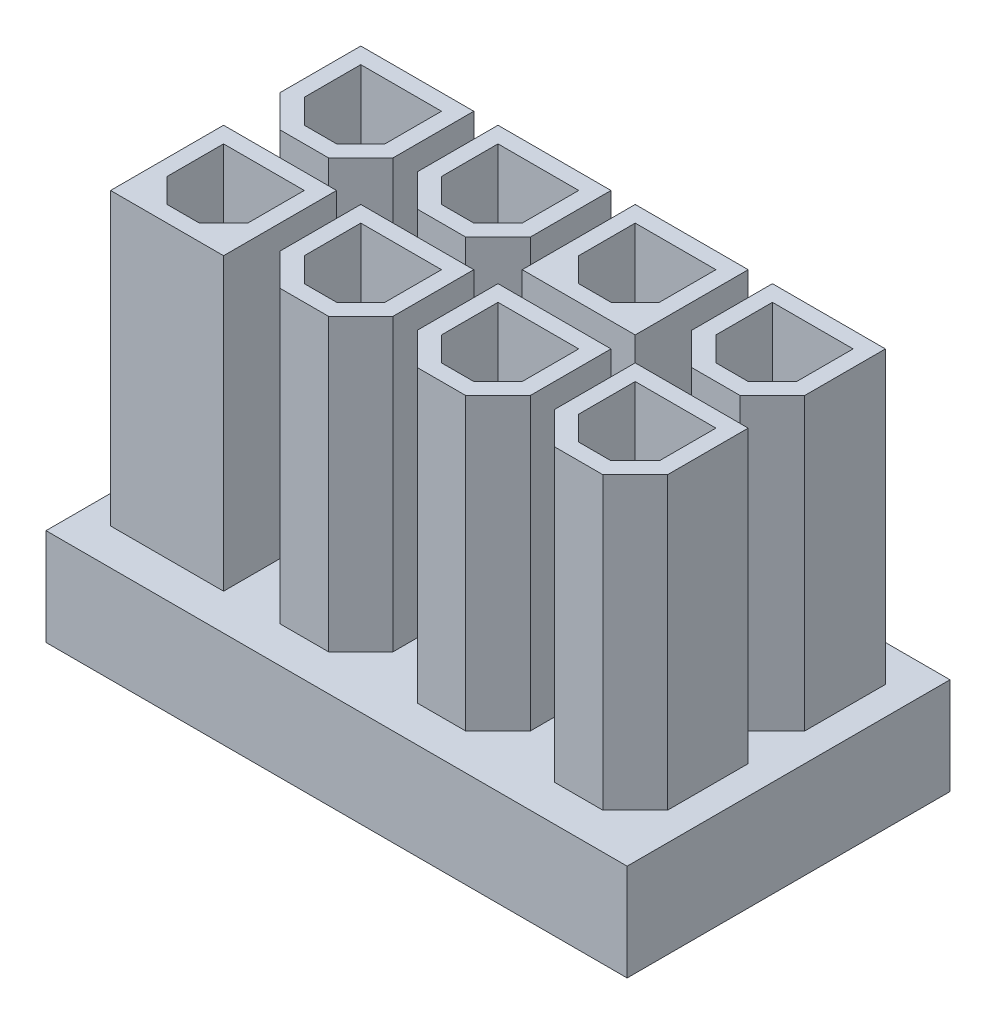
SolidWorks part; units mm, degrees
ref_plane "Ebene vorne" through (0, 0, 0) normal (0, 0, 1) x (1, 0, 0)
ref_plane "Ebene oben" through (0, 0, 0) normal (0, 1, 0) x (1, 0, 0)
ref_plane "Ebene rechts" through (0, 0, 0) normal (1, 0, 0) x (0, 0, -1)
sketch "Skizze1" plane through (0, 0, 0) normal (1, 0, 0) x (0, 0, -1)
  line L1 (5, 0) -> (-5, 0)
  line L2 (5, 0) -> (5, 11)
  line L3 (5, 11) -> (-5, 11)
  line L4 (-5, 0) -> (-5, 11)
  point P4 (0, 0)
  dimension "D1" = 10
  dimension "D2" = 11
extrude "Aufsatz-Linear austragen1" add sketch "Skizze1" along normal mid plane 18
sketch "Skizze2" plane through (0, 0, 0) normal (1, 0, 0) x (0, 0, -1)
  line L0 (0, 0) -> (0, 11) construction
  line L1 (-5, 0) -> (-6.5, 0)
  line L2 (-5, 0) -> (-5, 1)
  line L3 (-5, 1) -> (-6.5, 1)
  line L4 (-6.5, 0) -> (-6.5, 1)
  line L5 (5, 11) -> (-5, 11) construction
  line L6 (6.5, 0) -> (6.5, 1)
  line L7 (5, 1) -> (6.5, 1)
  line L8 (5, 0) -> (5, 1)
  line L9 (5, 0) -> (6.5, 0)
  dimension "D1" = 1.5
  dimension "D2" = 1
extrude "Aufsatz-Linear austragen2" add sketch "Skizze2" along normal mid plane 18
sketch "Skizze3" plane through (0, 0, 0) normal (1, 0, 0) x (0, 0, -1)
  line L0 (5, 11) -> (5.5717, 11)
  line L1 (7.5, 8.198) -> (7.5, 5.198)
  line L2 (7.5, 5.198) -> (8.5, 4)
  line L3 (8.5, 4) -> (8.5, 2)
  line L4 (8.5, 2) -> (6.5, 2)
  line L5 (6.5, 2) -> (6.5, 8)
  line L6 (6.5, 8) -> (5, 8)
  line L7 (5, 1) -> (5, 11) construction
  line L8 (5, 11) -> (5, 8)
  line L9 (-6.5, 0) -> (6.5, 0) construction
  arc A0 (5.5717, 11) -> (6.5359, 9.599) centre (7.0717, 11) ccw
  arc A1 (6.5359, 9.599) -> (7.5, 8.198) centre (6, 8.198) cw
  dimension "D5" = 1.5
  dimension "D1" = 2
  dimension "D2" = 1
  dimension "D3" = 2
  dimension "D4" = 2
  dimension "D6" = 3
  dimension "D7" = 1.5
  dimension "D8" = 3
extrude "Aufsatz-Linear austragen3" [suppressed] add sketch "Skizze3" along normal mid plane 8
sketch "Skizze4" [suppressed] plane through (0, 0, 0) normal (0, -1, 0) x (1, 0, 0)
  line L0 (9, -5) -> (-9, -5) construction
  line L1 (-2.5, -5) -> (2.5, -5)
  line L2 (-2.5, -5) -> (-2.5, -6.5)
  line L3 (-2.5, -6.5) -> (2.5, -6.5)
  line L4 (2.5, -5) -> (2.5, -6.5)
  line L5 (9, -6.5) -> (-9, -6.5) construction
  line L6 (0, -5) -> (0, 0) construction
  line L7 (-4, -6.5) -> (-4, -8.5) construction
  dimension "D1" = 1.5
extrude "Schnitt-Linear austragen1" [suppressed] cut sketch "Skizze4" against normal through all
sketch "Skizze5" [suppressed] plane through (0, 0, 0) normal (1, 0, 0) x (0, 0, -1)
  line L0 (8.1235, 4.451) -> (8.1235, 19.8707)
  line L1 (8.5, 4) -> (7.5, 5.198) construction
  line L2 (8.1235, 19.8707) -> (7.1363, 21)
  line L3 (7.1363, 21) -> (6.1363, 21)
  line L4 (6.1363, 21) -> (4.6235, 19.6776)
  line L5 (4.6235, 19.6776) -> (4.6235, 17.6776)
  line L6 (4.6235, 17.6776) -> (6.1235, 17.6776)
  line L7 (6.1235, 17.6776) -> (6.5, 8)
  line L8 (6.5, 8) -> (6.5, 2)
  line L9 (6.5, 2) -> (8.1235, 4.451)
  line L10 (5, 11) -> (-5, 11) construction
  dimension "D1" = 3.5
  dimension "D2" = 1.5
  dimension "D3" = 1
  dimension "D4" = 10
  dimension "D5" = 2
  dimension "D6" = 2.0093
  dimension "D7" = 1.5
extrude "Aufsatz-Linear austragen4" [suppressed] add sketch "Skizze5" along normal mid plane 5
sketch "Skizze6" plane through (0, 0, 0) normal (0, -1, 0) x (1, 0, 0)
  line L0 (-9, 6.5) -> (-9, -6.5) construction
  line L1 (-8.25, -4) -> (-4.5, -4)
  line L2 (-8.25, -4) -> (-8.25, -0.25)
  line L3 (-8.25, -0.25) -> (-4.5, -0.25)
  line L4 (-4.5, -4) -> (-4.5, -0.25)
  line L5 (9, -5) -> (-9, -5) construction
  dimension "D1" = 0.75
  dimension "D2" = 1
  dimension "D3" = 3.75
extrude "Schnitt-Linear austragen2" cut sketch "Skizze6" against normal blind 10
pattern_linear "Lineares Muster1" count 4 spacing 4.25 along (1, 0, 0) count 2 spacing 4.25 along (0, 0, 1) of "Schnitt-Linear austragen2"
sketch "Skizze7" plane through (0, 11, 0) normal (0, 1, 0) x (1, 0, 0)
  line L1 (-4.5, -0.25) -> (-8.25, -4) construction
  line L2 (-8.25, -0.25) -> (-4.5, -4) construction
  line L4 (-8.125, -0.375) -> (-4.625, -0.375)
  line L6 (-8.125, -0.375) -> (-8.125, -3.875)
  line L8 (-8.125, -3.875) -> (-4.625, -3.875)
  line L10 (-4.625, -0.375) -> (-4.625, -3.875)
  line L11 (-8.125, -0.375) -> (-4.625, -3.875) construction
  point P4 (-6.375, -2.125)
  dimension "D1" = 3.5
extrude "Aufsatz-Linear austragen5" add sketch "Skizze7" along normal blind 9
pattern_linear "Lineares Muster2" count 3 spacing 4.25 along (1, 0, 0) count 2 spacing 4.25 along (0, 0, -1) of "Aufsatz-Linear austragen5"
sketch "Skizze10" plane through (0, 11, 0) normal (0, 1, 0) x (1, 0, 0)
  line L0 (-8.25, 4) -> (-4.5, 0.25) construction
  line L1 (-4.5, 4) -> (-8.25, 0.25) construction
  line L3 (-4.625, 1.375) -> (-5.625, 0.375)
  line L5 (-5.625, 0.375) -> (-7.125, 0.375)
  line L6 (-4.625, 1.375) -> (-4.625, 3.875)
  line L7 (-4.625, 3.875) -> (-8.125, 3.875)
  line L8 (-8.125, 1.375) -> (-8.125, 3.875)
  line L9 (-4.625, 0.375) -> (-8.125, 3.875) construction
  line L10 (-4.625, 3.875) -> (-8.125, 0.375) construction
  line L11 (-7.125, 0.375) -> (-8.125, 1.375)
  point P4 (-6.375, 2.125)
  dimension "D1" = 3.5
extrude "Aufsatz-Linear austragen7" add sketch "Skizze10" along normal up to surface (9 mm away) up to face at (-6.375, 20, 2.125)
pattern_linear "Lineares Muster4" count 4 spacing 4.25 along (1, 0, 0) count 2 spacing 4.25 along (0, 0, 1) skipping (0, 1), (2, 0) of "Aufsatz-Linear austragen7"
sketch "Skizze12" plane through (0, 20, 0) normal (0, 1, 0) x (1, 0, 0)
  line L16 (-8.25, 2.125) -> (-4.5, 2.125) construction
  line L17 (-6.375, 4) -> (-6.375, 0.25) construction
  line L18 (-8.25, 4) -> (-3.0668, -1.1832) construction
  line L19 (-5.875, 0.875) -> (-5.125, 1.625)
  line L20 (-7.625, 3.375) -> (-5.125, 3.375)
  line L21 (-7.625, 3.375) -> (-7.625, 1.625)
  line L22 (-6.875, 0.875) -> (-5.875, 0.875)
  line L23 (-5.125, 3.375) -> (-5.125, 1.625)
  line L24 (-7.625, 3.375) -> (-5.125, 0.875) construction
  line L25 (-7.625, 0.875) -> (-5.125, 3.375) construction
  line L26 (-7.625, 1.625) -> (-6.875, 0.875)
  line L27 (-4.5, 4) -> (-4.5, 0.25) construction
  line L28 (-8.25, 0.25) -> (-8.25, 4) construction
  line L29 (-8.25, 4) -> (-4.5, 4) construction
  line L30 (-4.5, 0.25) -> (-8.25, 0.25) construction
  point P35 (-6.375, 2.125)
  dimension "D1" = 2.5
  dimension "D3" = 0.75
  dimension "D4" = 0.75
  dimension "D5" = 0.75
  dimension "D6" = 0.75
  dimension "D7" = 2.5
extrude "Schnitt-Linear austragen4" cut sketch "Skizze12" against normal through all
pattern_linear "Lineares Muster6" count 4 spacing 4.25 along (1, 0, 0) count 2 spacing 4.25 along (0, 0, 1) of "Schnitt-Linear austragen4"
sketch "草图2" plane through (0, 10, 0) normal (0, -1, 0) x (-1, 0, 0)
  point P8 (-6.375, -2.125)
  point P9 (-6.375, 2.125)
  point P10 (-2.125, 2.125)
  point P11 (-2.125, -2.125)
  point P12 (2.125, -2.125)
  point P13 (2.125, 2.125)
  point P14 (6.375, -2.125)
  point P15 (6.375, 2.125)
other "连接点1" parameters "直径"=2, "端头长度"=10
ref_axis "基准轴9" through (6.375, 0, -2.125) along (0, 1, 0)
other "连接点2" parameters "直径"=2, "端头长度"=10
ref_axis "基准轴10" through (6.375, 0, 2.125) along (0, 1, 0)
other "连接点3" parameters "直径"=2, "端头长度"=10
ref_axis "基准轴11" through (2.125, 0, 2.125) along (0, 1, 0)
other "连接点4" parameters "直径"=2, "端头长度"=10
ref_axis "基准轴12" through (2.125, 0, -2.125) along (0, 1, 0)
other "连接点5" parameters "直径"=2, "端头长度"=10
ref_axis "基准轴13" through (-2.125, 0, -2.125) along (0, 1, 0)
other "连接点6" parameters "直径"=2, "端头长度"=10
ref_axis "基准轴14" through (-2.125, 0, 2.125) along (0, 1, 0)
other "连接点7" parameters "直径"=2, "端头长度"=10
ref_axis "基准轴15" through (-6.375, 0, -2.125) along (0, 1, 0)
other "连接点8" parameters "直径"=2, "端头长度"=10
ref_axis "基准轴16" through (-6.375, 0, 2.125) along (0, 1, 0)
ref_axis "B2" through (6.375, 10, -2.125) along (0, -1, 0)
ref_axis "B3" through (2.125, 10, -2.125) along (0, -1, 0)
ref_axis "B4" through (-2.125, 10, -2.125) along (0, -1, 0)
ref_axis "B5" through (-6.375, 10, -2.125) along (0, -1, 0)
ref_axis "B1" through (6.375, 10, 2.125) along (0, -1, 0)
ref_axis "A1" through (2.125, 10, 2.125) along (0, -1, 0)
ref_axis "A2" through (-2.125, 10, 2.125) along (0, -1, 0)
ref_axis "A3" through (-6.375, 10, 2.125) along (0, -1, 0)
sketch "草图3" plane through (0, 0, 0) normal (0, -1, 0) x (-1, 0, 0)
  line L1 (9.6075, -10.9398) -> (-10.4636, -10.9398)
  line L2 (9.6075, -10.9398) -> (9.6075, 10.0906)
  line L3 (9.6075, 10.0906) -> (-10.4636, 10.0906)
  line L4 (-10.4636, -10.9398) -> (-10.4636, 10.0906)
extrude "切除-拉伸1" cut sketch "草图3" against normal blind 8
